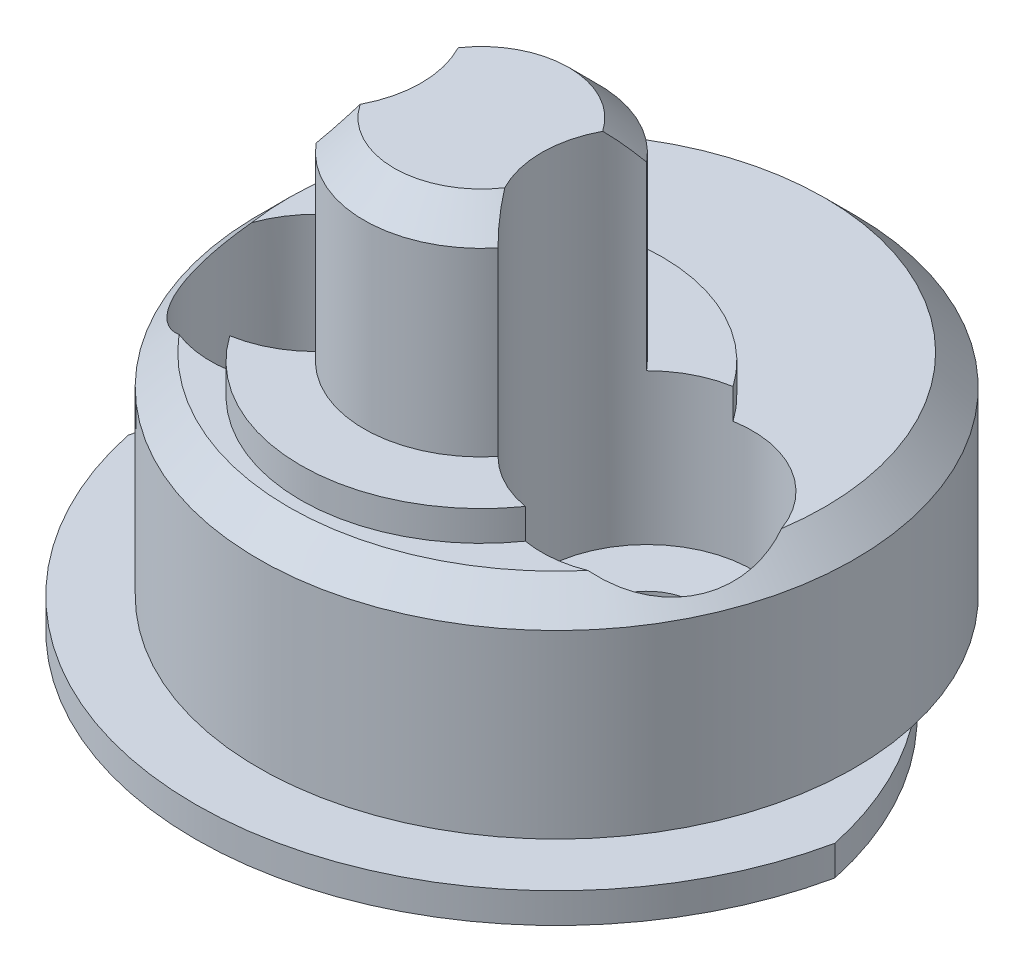
SolidWorks part; units mm, degrees
ref_plane "Front Plane" through (0, 0, 0) normal (0, 0, 1) x (1, 0, 0)
ref_plane "Top Plane" through (0, 0, 0) normal (0, 1, 0) x (1, 0, 0)
ref_plane "Right Plane" through (0, 0, 0) normal (1, 0, 0) x (0, 0, -1)
sketch "Sketch1" plane through (0, 0, 0) normal (0, 1, 0) x (1, 0, 0)
  circle A0 centre (0, 0) radius 3.9
  dimension "D1" = 7.8
extrude "Boss-Extrude1" add sketch "Sketch1" along normal blind 7
sketch "Sketch2" plane through (0, 0, 0) normal (0, -1, 0) x (-1, 0, 0)
  circle A0 centre (0, 0) radius 6
  dimension "D1" = 12
extrude "Boss-Extrude2" add sketch "Sketch2" along normal blind 1
sketch "Sketch3" plane through (0, -1, 0) normal (0, -1, 0) x (-1, 0, 0)
  circle A0 centre (0, 2.5) radius 9.9
  dimension "D1" = 19.8
  dimension "D2" = 2.5
extrude "Boss-Extrude3" add sketch "Sketch3" along normal blind 7
sketch "Sketch4" plane through (0, -8, 0) normal (0, -1, 0) x (-1, 0, 0)
  arc A2 (-11.7367, 0) -> (11.7367, 0) centre (0, 2.5) ccw
  arc A3 (11.7367, 0) -> (-11.7367, 0) centre (0, -2.5) ccw
  dimension "D1" = 24
  dimension "D2" = 24
  dimension "D3" = 2.5
extrude "Boss-Extrude4" add sketch "Sketch4" along normal blind 1
sketch "Sketch5" plane through (0, 0, 0) normal (0, 1, 0) x (1, 0, 0)
  circle A0 centre (5.5, 0) radius 1.6
  circle A1 centre (-5.5, 0) radius 1.6
  dimension "D1" = 3.2
  dimension "D2" = 3.2
  dimension "D3" = 5.5
  dimension "D4" = 5.5
extrude "Cut-Extrude1" cut sketch "Sketch5" against normal through all
sketch "Sketch7" plane through (0, 0, 0) normal (0, 1, 0) x (1, 0, 0)
  circle A0 centre (-5.5, 0) radius 3.5
  circle A1 centre (5.5, 0) radius 3.5
  dimension "D1" = 7
  dimension "D2" = 7
extrude "Cut-Extrude2" cut sketch "Sketch7" against normal blind 5 and the other way through all
chamfer "Chamfer1" distance 1 angle 45 3 edges at (0, -1, -12.4) (0, 7, 3.9) (0, 7, -3.9)
equation "\"e\" = 2.5"
equation "\"D3@Sketch4\"=\"e\""
equation "\"D2@Sketch3\"=\"e\""
